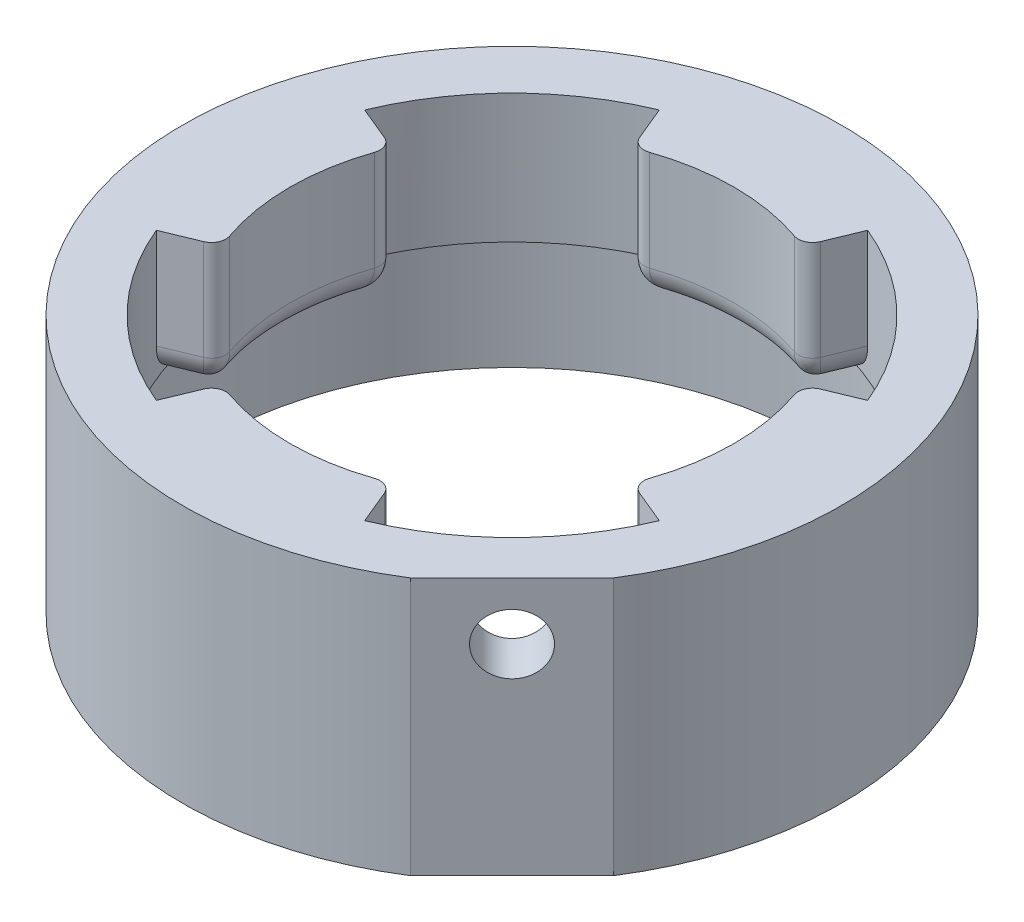
SolidWorks part; units mm, degrees
ref_plane "Front Plane" through (0, 0, 0) normal (0, 0, 1) x (1, 0, 0)
ref_plane "Top Plane" through (0, 0, 0) normal (0, 1, 0) x (1, 0, 0)
ref_plane "Right Plane" through (0, 0, 0) normal (1, 0, 0) x (0, 0, -1)
sketch "Sketch1" plane through (0, 0, 0) normal (0, 0, 1) x (1, 0, 0)
  line L0 (0, 0) -> (0, 19) construction
  line L1 (21, 0) -> (23, 0)
  line L2 (23, 0) -> (23, 18)
  line L3 (23, 18) -> (19, 18)
  line L4 (19, 18) -> (19, 9)
  line L5 (19, 9) -> (21, 9)
  line L6 (21, 9) -> (21, 0)
  point P9 (20, 9)
  dimension "D1" = 19
  dimension "D2" = 19
  dimension "D3" = 23
  dimension "D4" = 21
  dimension "D5" = 9
  dimension "D6" = 9
revolve "Revolve1" add sketch "Sketch1" angle 360 about L0
sketch "Sketch2" plane through (0, 18, 0) normal (0, 1, 0) x (1, 0, 0)
  line L0 (0, 0) -> (-24, 0) construction
  line L1 (0, 0) -> (-23.4755, -4.9899)
  line L2 (0, 0) -> (-23.4755, 4.9899)
  line L3 (0, 0) -> (-20.1281, 13.0713)
  line L4 (0, 0) -> (-13.0713, 20.1281)
  line L5 (0, 0) -> (-4.9899, 23.4755)
  line L6 (0, 0) -> (4.9899, 23.4755)
  line L7 (0, 0) -> (13.0713, 20.1281)
  line L8 (0, 0) -> (20.1281, 13.0713)
  line L9 (0, 0) -> (23.4755, 4.9899)
  line L10 (0, 0) -> (23.4755, -4.9899)
  line L11 (0, 0) -> (20.1281, -13.0713)
  line L12 (0, 0) -> (13.0713, -20.1281)
  line L13 (0, 0) -> (4.9899, -23.4755)
  line L14 (0, 0) -> (-4.9899, -23.4755)
  line L15 (0, 0) -> (-13.0713, -20.1281)
  line L16 (0, 0) -> (-20.1281, -13.0713)
  circle A0 centre (0, 0) radius 23 construction
  circle A1 centre (0, 0) radius 23
  circle A2 centre (0, 0) radius 24
  circle A3 centre (0, 0) radius 22
  point P24 (0, 0)
  circle M3 centre (0, 0) radius 23
  dimension "D1" = 48
  dimension "D2" = 44
  dimension "D3" = 12
  dimension "D4" = 8
extrude "Boss-Extrude1" [suppressed] add sketch "Sketch2" against normal up to surface (15 mm away) contours A1 L0 A2 L1 | L0 L2 A2 M3 | L16 A2 L15 M3 | L14 A2 L13 M3 | L12 A2 L11 M3 | L10 A2 L9 M3 | L8 A2 L7 M3 | L6 A2 L5 M3 | L4 A2 L3 M3 up to face at (0, 0, -23)
sketch "Sketch3" plane through (0, 18, 0) normal (0, 1, 0) x (1, 0, 0)
  line L0 (0, 0) -> (-7.271, 17.5537)
  line L1 (0, 0) -> (0, 19) construction
  line L2 (0, 0) -> (7.271, 17.5537)
  line L3 (0, 0) -> (17.5537, -7.271)
  line L4 (0, 0) -> (17.5537, 7.271)
  line L5 (0, 0) -> (-7.271, -17.5537)
  line L6 (0, 0) -> (7.271, -17.5537)
  line L7 (0, 0) -> (-17.5537, 7.271)
  line L8 (0, 0) -> (-17.5537, -7.271)
  circle A0 centre (0, 0) radius 15.5
  circle A1 centre (0, 0) radius 19 construction
  circle A2 centre (0, 0) radius 19
  point P18 (0, 0)
  circle M5 centre (0, 0) radius 19
  dimension "D1" = 31
  dimension "D2" = 22.5
  dimension "D3" = 4
extrude "Boss-Extrude2" add sketch "Sketch3" against normal up to surface (9 mm away) contours A0 L7 L8 M5 | A0 L5 L6 M5 | A0 L3 L4 M5 | L1 A0 L2 A2 | A0 L1 L0 M5 region at (-3.3552, 18, -16.8677) region at (3.3552, 18, -16.8677) region at (16.8677, 18, 0) region at (0, 18, 16.8677) region at (-16.8677, 18, 0) up to face at (0, 9, -21)
fillet "Fillet1" radius 1 8 edges at (5.9316, 13.5, 14.3201) (-5.9316, 13.5, 14.3201) (-14.3201, 13.5, -5.9316) (-14.3201, 13.5, 5.9316) (14.3201, 13.5, 5.9316) (14.3201, 13.5, -5.9316) (5.9316, 13.5, -14.3201) (-5.9316, 13.5, -14.3201)
fillet "Fillet3" [suppressed] radius 1
sketch "Sketch4" plane through (0, 0, 0) normal (0, 1, 0) x (1, 0, 0)
  line L0 (0, 0) -> (23, 0) construction
  line L1 (22.4499, -5) -> (22.4499, 5)
  circle A0 centre (0, 0) radius 23 construction
  circle A1 centre (0, 0) radius 23
  point P7 (22.4499, 0)
  dimension "D1" = 10
extrude "Cut-Extrude1" [suppressed] cut sketch "Sketch4" along normal through all contours L1 L0 A1 | L0 L1 A1
sketch "Sketch5" [suppressed] plane through (22.4499, 0, 0) normal (1, 0, 0) x (0, 0, -1)
  line L0 (0, 9) -> (0, 17) construction
  line L2 (-5.0528, 9) -> (5.0528, 9) construction
  line L3 (-5.0528, 9) -> (5.0528, 9)
  line L4 (-5, 17) -> (5, 17) construction
  circle A0 centre (0, 13.5) radius 2
  dimension "D1" = 4
  dimension "D2" = 4.5
extrude "Cut-Extrude2" [suppressed] cut sketch "Sketch5" against normal up to surface (7.0795 mm away) contours A0 L0 | L0 A0 up to face at (15.0766, 13.5, 0)
sketch "Sketch6" plane through (0, 0, 0) normal (0, 1, 0) x (1, 0, 0)
  line L0 (13.435, -13.435) -> (0, 0) construction
  line L1 (13.435, -13.435) -> (16.2635, -16.2635) construction
  line L2 (12.339, -19.41) -> (19.41, -12.339)
  circle A0 centre (0, 0) radius 23 construction
  circle A1 centre (0, 0) radius 23
  arc A2 (7.271, -17.5537) -> (17.5537, -7.271) centre (0, 0) ccw construction
  point P11 (15.8745, -15.8745)
  dimension "D1" = 10
extrude "Cut-Extrude3" cut sketch "Sketch6" along normal through all contours L2 A1 region at (16.0302, 0, 16.0302)
sketch "Sketch7" plane through (15.8745, 0, 15.8745) normal (0.7071, 0, 0.7071) x (0.7071, 0, -0.7071)
  line L0 (0, 9) -> (0, 14) construction
  line L2 (-21, 9) -> (21, 9) construction
  circle A0 centre (0, 14) radius 2.1
  dimension "D2" = 4.2
  dimension "D1" = 5
extrude "Cut-Extrude4" cut sketch "Sketch7" against normal up to surface (3.5664 mm away) up to face at (12.9237, 13.5, 12.9237)
fillet "Fillet4" radius 2 20 edges at (-16.3849, 9, -6.7868) (-14.6868, 9, -5.7893) (-16.3849, 9, 6.7868) (-14.6868, 9, 5.7893) (6.7868, 9, -16.3849) (5.7893, 9, -14.6868) (-6.7868, 9, -16.3849) (-5.7893, 9, -14.6868) (16.3849, 9, 6.7868) (14.6868, 9, 5.7893) (16.3849, 9, -6.7868) (14.6868, 9, -5.7893) (-6.7868, 9, 16.3849) (-5.7893, 9, 14.6868) (6.7868, 9, 16.3849) (5.7893, 9, 14.6868) (-15.5, 9, 0) (0, 9, -15.5) (15.5, 9, 0) (0, 9, 15.5)
